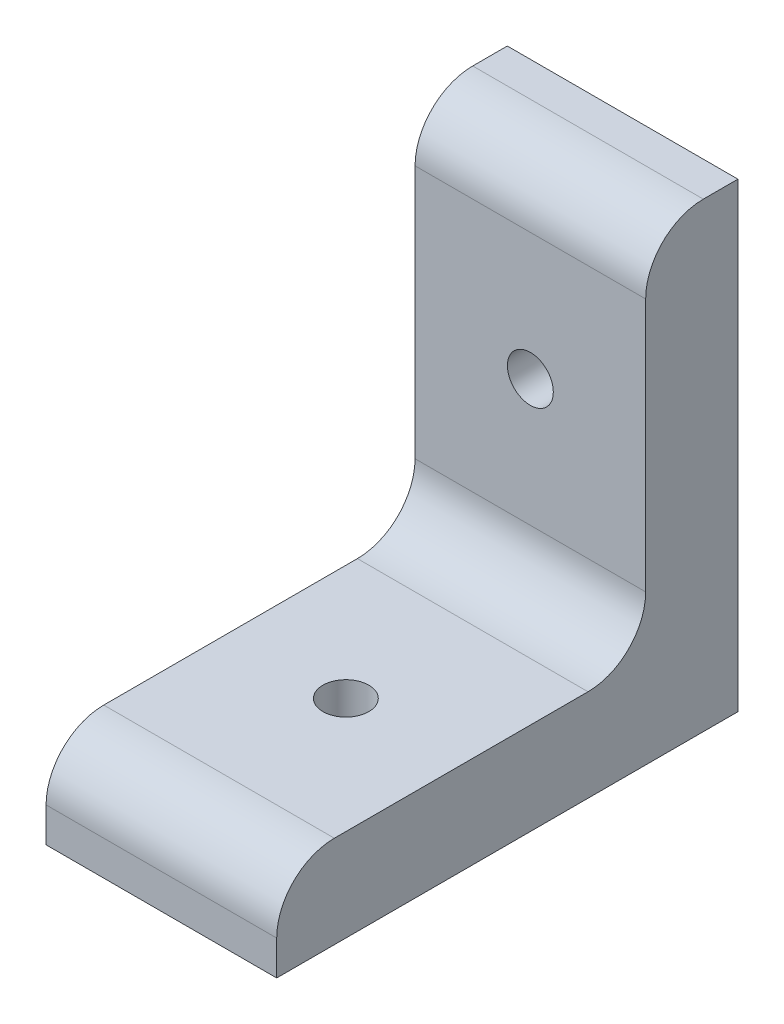
SolidWorks part; units mm, degrees
ref_plane "Front Plane" through (0, 0, 0) normal (0, 0, 1) x (1, 0, 0)
ref_plane "Top Plane" through (0, 0, 0) normal (0, 1, 0) x (1, 0, 0)
ref_plane "Right Plane" through (0, 0, 0) normal (1, 0, 0) x (0, 0, -1)
sketch "Sketch1" plane through (0, 0, 0) normal (1, 0, 0) x (0, 0, -1)
  line L0 (0, 0) -> (0, 50.8)
  line L9 (0, 50.8) -> (-10.16, 50.8)
  line L10 (-10.16, 50.8) -> (-10.16, 10.16)
  line L11 (-10.16, 10.16) -> (-50.8, 10.16)
  line L12 (-50.8, 10.16) -> (-50.8, 0)
  line L13 (-50.8, 0) -> (0, 0)
  dimension "D1" = 50.8
  dimension "D2" = 50.8
  dimension "D3" = 10.16
  dimension "D4" = 10.16
extrude "Boss-Extrude1" add sketch "Sketch1" along normal blind 25.4
sketch "Sketch2" plane through (0, 0, 10.16) normal (0, 0, 1) x (1, 0, 0)
  line L0 (12.7, 10.16) -> (12.7, 50.8) construction
  line L1 (25.4, 10.16) -> (0, 10.16) construction
  line L2 (25.4, 50.8) -> (0, 50.8) construction
  line L3 (25.4, 30.48) -> (0, 30.48) construction
  line L4 (25.4, 50.8) -> (25.4, 10.16) construction
  line L5 (0, 50.8) -> (0, 10.16) construction
  point P12 (12.7, 30.48)
sketch "Sketch3" plane through (0, 10.16, 0) normal (0, 1, 0) x (1, 0, 0)
  line L0 (25.4, -10.16) -> (0, -10.16) construction
  line L1 (0, -50.8) -> (25.4, -50.8)
  line L2 (0, -50.8) -> (0, -10.16)
  line L3 (0, -10.16) -> (25.4, -10.16)
  line L4 (25.4, -50.8) -> (25.4, -10.16)
  line L5 (0, -50.8) -> (25.4, -10.16) construction
  line L6 (0, -10.16) -> (25.4, -50.8) construction
  line L7 (25.4, -10.16) -> (25.4, -50.8) construction
  line L8 (0, -10.16) -> (0, -50.8) construction
  line L9 (25.4, -50.8) -> (0, -50.8) construction
  point P0 (12.7, -30.48)
  point P13 (12.7, -30.48)
fillet "Fillet1" radius 6.35 3 edges at (12.7, 50.8, 10.16) (12.7, 10.16, 50.8) (12.7, 10.16, 10.16)
hole_wizard "#8 (0.199) Diameter Hole1" positions "Sketch4" profile "Sketch5" hole size "#8" standard "ANSI Inch" end condition through all
sketch "Sketch4" plane through (0, 0, 10.16) normal (0, 0, 1) x (1, 0, 0)
  point P0 (12.7, 30.48)
sketch "Sketch5" plane through (12.7, 30.48, 10.16) normal (1, 0, 0) x (0, -1, 0)
  line L0 (0, 0) -> (0, 10.16)
  line L1 (0, 10.16) -> (2.5273, 10.16)
  line L2 (2.5273, 10.16) -> (2.5273, 0)
  line L5 (2.5273, 0) -> (0, 0)
  line L11 (0, -6.35) -> (0, 107.95) construction
  dimension "Thru Hole Dia." = 5.0546
  dimension "Thru Hole Depth" = 10.16
hole_wizard "#8 (0.199) Diameter Hole2" positions "Sketch6" profile "Sketch7" hole size "#8" standard "ANSI Inch" end condition through all
sketch "Sketch6" plane through (0, 10.16, 0) normal (0, 1, 0) x (1, 0, 0)
  point P0 (12.7, -30.48)
sketch "Sketch7" plane through (12.7, 10.16, 30.48) normal (1, 0, 0) x (0, 0, 1)
  line L0 (0, 0) -> (0, 10.16)
  line L1 (0, 10.16) -> (2.5273, 10.16)
  line L2 (2.5273, 10.16) -> (2.5273, 0)
  line L5 (2.5273, 0) -> (0, 0)
  line L11 (0, -6.35) -> (0, 107.95) construction
  dimension "Thru Hole Dia." = 5.0546
  dimension "Thru Hole Depth" = 10.16
